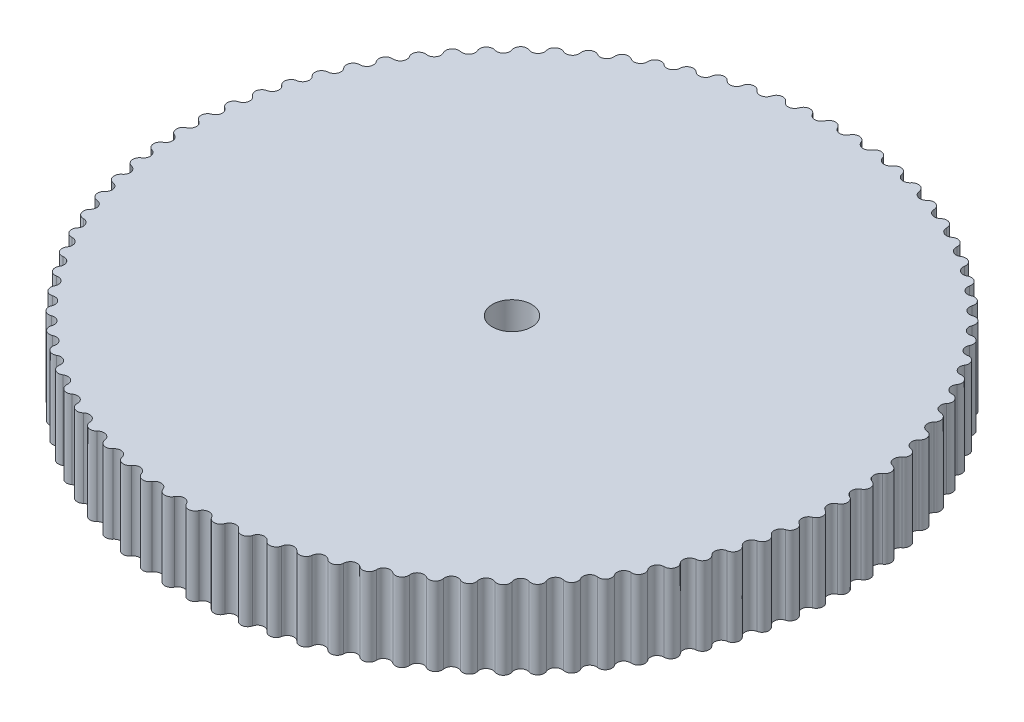
SolidWorks part; units mm, degrees
note: '?' marks a value the reader was unsure of.
ref_plane "Front Plane" through (0, 0, 0) normal (0, 0, 1) x (1, 0, 0)
ref_plane "Top Plane" through (0, 0, 0) normal (0, 1, 0) x (1, 0, 0)
ref_plane "Right Plane" through (0, 0, 0) normal (1, 0, 0) x (0, 0, -1)
sketch "Sketch1" plane through (0, 0, 0) normal (0, 1, 0) x (1, 0, 0)
  line L0 (0, 20.5) -> (0, 21) construction
  line L1 (0.7665, 20.4857) -> (0.7852, 20.9853) construction
  line L2 (1.532, 20.4427) -> (1.5693, 20.9413) construction
  line L3 (0, 20.75) -> (0, 1.25)
  line L4 (0.0934, 1.2465) -> (1.5506, 20.692)
  circle A0 centre (0, 0) radius 20.5 construction
  arc A1 (0, 20.75) -> (0.7759, 20.7355) centre (0.3913, 20.9251) ccw
  arc A2 (1.5693, 20.9413) -> (0, 21) centre (0, 0) ccw construction
  arc A3 (0.7759, 20.7355) -> (1.5506, 20.692) centre (1.1537, 20.544) cw
  arc A4 (0.0934, 1.2465) -> (0, 1.25) centre (0, 0) ccw
  point P6 (0, 20.75)
  point P9 (0.7759, 20.7355)
  dimension "D1" = 41
  dimension "D2" = 0.5
  dimension "D3" = 2.5
extrude "Boss-Extrude1" add sketch "Sketch1" along normal blind 5
pattern_circular "CirPattern1" count 84 over 360 about axis through (0, 0, 0) along (0, 1, 0) of "Boss-Extrude1"
ref_axis "Axis1" through (0, 0, 0) along (0, 1, 0)?
sketch "Sketch2" plane through (0, 5, 0) normal (0, 1, 0) x (1, 0, 0)
  line L0 (0, 74.1691) -> (0, -78.0459) construction
  line L1 (4.7625, 3.175) -> (6.6675, 3.175)
  line L2 (4.7625, 3.175) -> (4.7625, -3.175)
  line L3 (4.7625, -3.175) -> (6.6675, -3.175)
  line L4 (6.6675, 3.175) -> (6.6675, -3.175)
  line L5 (-6.6675, 3.175) -> (-6.6675, -3.175)
  line L6 (-4.7625, -3.175) -> (-6.6675, -3.175)
  line L7 (-4.7625, 3.175) -> (-4.7625, -3.175)
  line L8 (-4.7625, 3.175) -> (-6.6675, 3.175)
  point P6 (4.7625, 0)
  point P12 (-4.7625, 0)
  dimension "D1" = 1.905
  dimension "D2" = 6.35
  dimension "D3" = 4.7625
